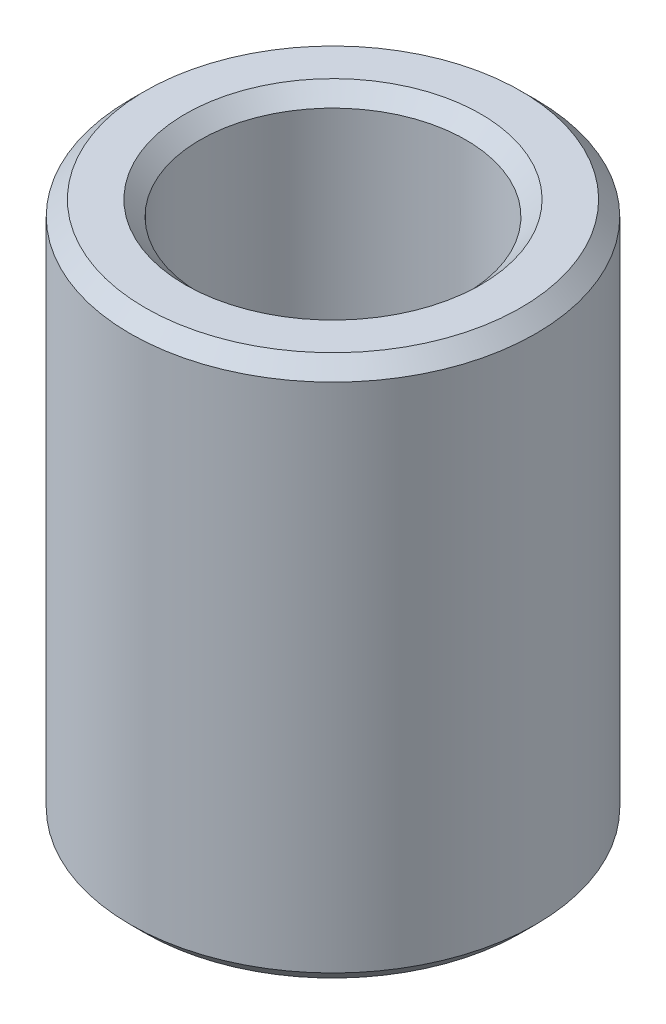
SolidWorks part; units mm, degrees
ref_plane "Front Plane" through (0, 0, 0) normal (0, 0, 1) x (1, 0, 0)
ref_plane "Top Plane" through (0, 0, 0) normal (0, 1, 0) x (1, 0, 0)
ref_plane "Right Plane" through (0, 0, 0) normal (1, 0, 0) x (0, 0, -1)
sketch "Sketch1" plane through (0, 0, 0) normal (0, 1, 0) x (1, 0, 0)
  circle A0 centre (0, 0) radius 37.5
  dimension "SLEEVE_OD" = 75
extrude "Boss-Extrude1" add sketch "Sketch1" along normal blind 100.153
sketch "Sketch2" plane through (0, 0, 0) normal (0, 1, 0) x (1, 0, 0)
  circle A0 centre (0, 0) radius 24.5817
  dimension "BORE_D" = 49.1633
extrude "Cut-Extrude1" cut sketch "Sketch2" along normal through all
chamfer "Chamfer1" distance 2.7639 angle 45 4 edges at (0, 100.153, 24.5817) (0, 0, 24.5817) (0, 0, 37.5) (0, 100.153, 37.5)
